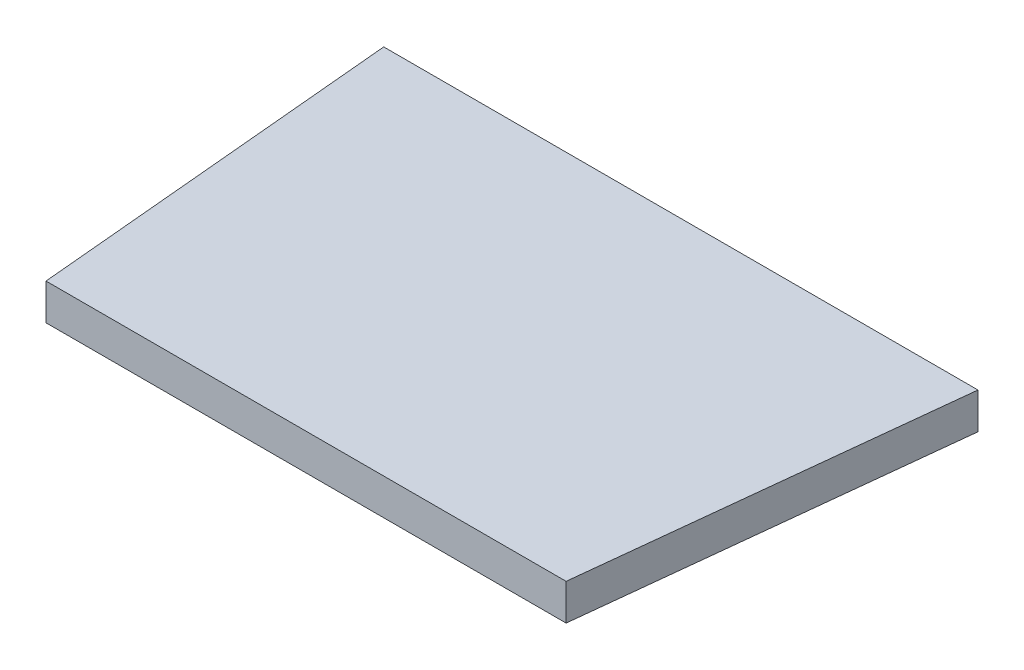
SolidWorks part; units mm, degrees
ref_plane "Front Plane" through (0, 0, 0) normal (0, 0, 1) x (1, 0, 0)
ref_plane "Top Plane" through (0, 0, 0) normal (0, 1, 0) x (1, 0, 0)
ref_plane "Right Plane" through (0, 0, 0) normal (1, 0, 0) x (0, 0, -1)
sketch "Sketch2" plane through (0, 0, 0) normal (0, 1, 0) x (1, 0, 0)
  line L0 (47.461, 35.6071) -> (-34.6527, 35.6071)
  line L2 (-34.6527, 35.6071) -> (-29.9685, -15.7438)
  line L3 (9.1113, -15.7438) -> (-29.9685, -15.7438)
  line L4 (9.1113, -15.7438) -> (41.8979, -15.7438)
  line L6 (41.8979, -15.7438) -> (47.461, 35.6071)
  line L8 (45.3562, -2.9841) -> (42.0339, -15.2419) construction
  point P0 (47.461, 35.6071)
extrude "Boss-Extrude1" add sketch "Sketch2" along normal blind 5
